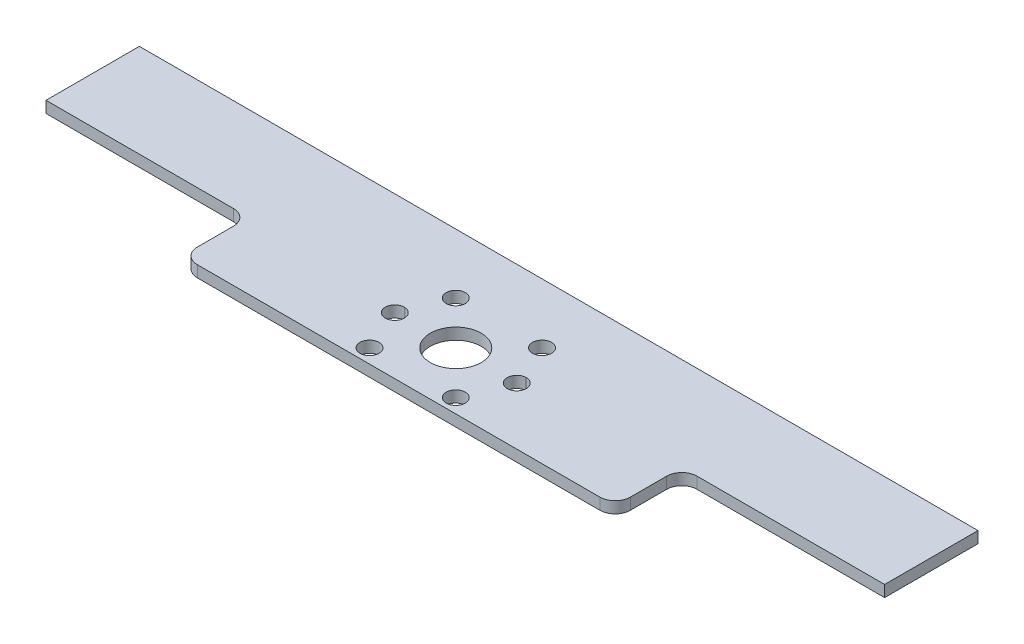
SolidWorks part; units mm, degrees
ref_plane "前视基准面" through (0, 0, 0) normal (0, 0, 1) x (1, 0, 0)
ref_plane "上视基准面" through (0, 0, 0) normal (0, 1, 0) x (1, 0, 0)
ref_plane "右视基准面" through (0, 0, 0) normal (1, 0, 0) x (0, 0, -1)
other "Configuration Table"
sketch "草图2" plane through (0, 0, 0) normal (0, 1, 0) x (1, 0, 0)
  line L0 (110, -9.2483) -> (-110, -9.2483)
  line L1 (110, -26.7483) -> (-110, -26.7483)
  line L2 (110, -26.7483) -> (110, 15.2517)
  line L3 (110, 15.2517) -> (-110, 15.2517)
  line L4 (-110, -26.7483) -> (-110, 15.2517)
  line L7 (56.8055, -9.2483) -> (56.8055, -26.7483)
  line L8 (0, -9.2483) -> (0, 15.2517)
  line L9 (-56.8055, -9.2483) -> (-56.8055, -26.7483)
  circle A0 centre (0, -11.7483) radius 6.682
  circle A1 centre (11.3137, -0.4346) radius 2.5
  circle A2 centre (0, -11.7483) radius 16
  circle A3 centre (16, -11.7483) radius 2.5
  circle A4 centre (11.3137, -23.062) radius 2.5
  circle A5 centre (0, -27.7483) radius 2.5
  circle A6 centre (-11.3137, -23.062) radius 2.5
  circle A7 centre (-16, -11.7483) radius 2.5
  circle A8 centre (-11.3137, -0.4346) radius 2.5
  circle A9 centre (0, 4.2517) radius 2.5
  point P0 (0, 0)
  point P37 (0, -11.7483)
  dimension "D3" = 5
  dimension "D1" = 220
  dimension "D2" = 17.5
  dimension "D5" = 42
  dimension "D4" = 8
extrude "凸台-拉伸1" add sketch "草图2" along normal blind 3 contours A7 A2 A6 L1 A5 A4 A3 L0 A0 | A9 L8 A0 L0 A2 A1 | A9 A2 A8 L0 A0 L8 | A9 L8 L3 L4 L0 A2 A8 | A9 A2 A1 L0 L2 L3 L8 | L1 A5 | A4 A2 L1 L7 L0 A3 | A7 L0 L9 L1 A2 A6 | A9 region at (58.3863, 0, -3.4299) region at (35.6553, 0, 18.309) region at (-58.3863, 0, -3.4299) region at (15.4472, 0, 9.3085) region at (6.9935, 0, 3.4384) region at (0, 0, 26.1296) region at (-6.9935, 0, 3.4384) region at (-35.6553, 0, 18.309)
fillet "圆角1" radius 4 4 edges at (56.8055, 1.5, 9.2483) (56.8055, 1.5, 26.7483) (-56.8055, 1.5, 9.2483) (-56.8055, 1.5, 26.7483)
